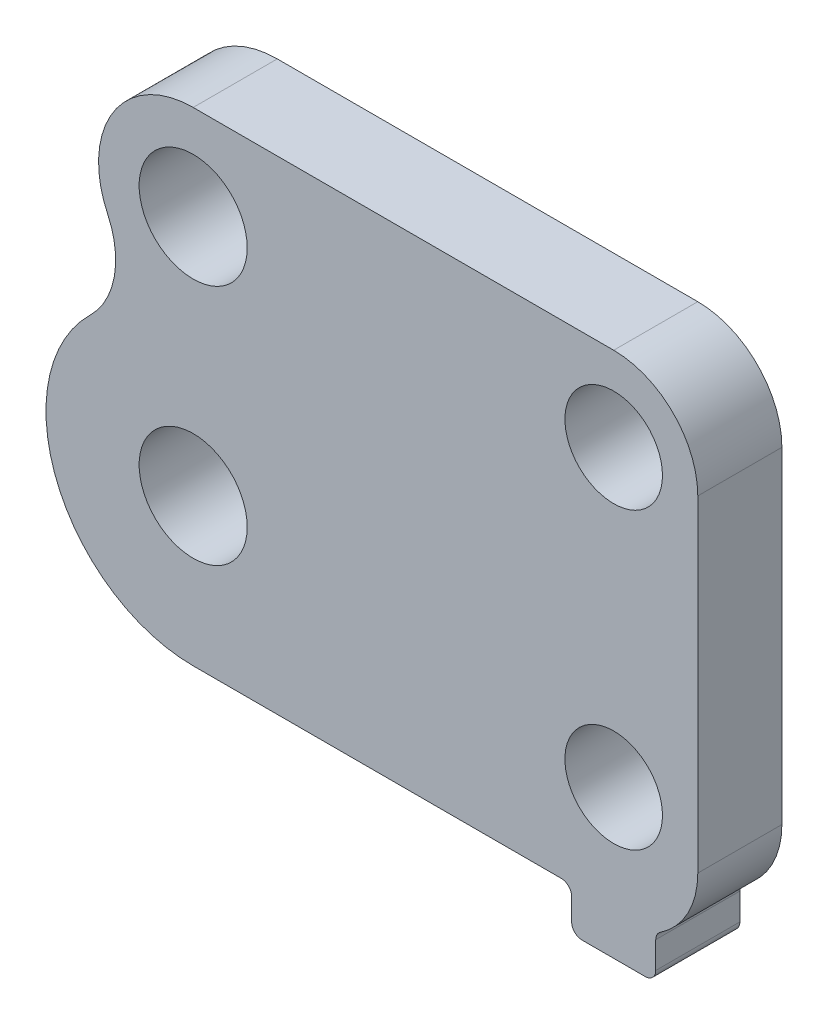
SolidWorks part; units mm, degrees
material "ABS"
ref_plane "Front Plane" through (0, 0, 0) normal (0, 0, 1) x (1, 0, 0)
ref_plane "Top Plane" through (0, 0, 0) normal (0, 1, 0) x (1, 0, 0)
ref_plane "Right Plane" through (0, 0, 0) normal (1, 0, 0) x (0, 0, -1)
sketch "Sketch2" plane through (0, 0, 0) normal (0, 0, 1) x (1, 0, 0)
  line L0 (0, 5.5562) -> (12.7, 5.5562)
  line L1 (12.7, 5.5562) -> (12.7, -5.5562) construction
  line L2 (12.7, -5.5562) -> (0, -5.5562)
  line L3 (12.7, 5.5562) -> (12.7, 13.4938)
  line L4 (12.7, 13.4938) -> (19.05, 13.4937)
  line L5 (19.05, 13.4937) -> (19.05, -5.5562)
  line L6 (19.05, -5.5562) -> (12.7, -5.5562)
  line L7 (15.875, 9.525) -> (15.875, -1.5875) construction
  line L8 (14.2875, -5.5562) -> (14.2875, -7.1818)
  line L9 (14.2875, -7.1818) -> (17.4625, -7.1818)
  line L10 (17.4625, -7.1818) -> (17.4625, -5.5562)
  line L11 (0, 0) -> (0, -9.1281) construction
  line L12 (7.1437, 12.7) -> (19.05, 12.7)
  line L13 (0, 12.7) -> (7.1437, 12.7)
  circle A0 centre (0, 0) radius 1.7859
  circle A1 centre (0, 0) radius 5.5562
  circle A2 centre (0, 9.1281) radius 1.7859
  circle A3 centre (0, 9.1281) radius 3.5719
  circle A4 centre (0, 0) radius 9.1281 construction
  circle A5 centre (15.875, 9.525) radius 1.5875
  circle A6 centre (15.875, -1.5875) radius 1.5875
  circle A7 centre (-6.1005, 6.2465) radius 3.175
  circle A8 centre (7.1437, 9.1281) radius 3.5719
  circle A9 centre (0, 0) radius 12.7 construction
  circle A10 centre (7.1437, 9.1281) radius 1.7859 construction
  point P17 (15.875, 3.9688)
  point P18 (19.05, 3.9688)
  point P21 (15.875, -5.5562)
  point P25 (15.875, -7.1818)
  dimension "D1" = 3.5719
  dimension "D2" = 11.1125
  dimension "D5" = 7.1437
  dimension "D7" = 3.175
  dimension "D6" = 6.35
  dimension "D3" = 11.1125
  dimension "D4" = 6.35
  dimension "D8" = 3.175
  dimension "D9" = 1.6256
  dimension "D10" = 19.05
sketch "Sketch3" plane through (0, 0, 0) normal (0, 0, 1) x (1, 0, 0)
  line L0 (7.1437, 12.7) -> (19.05, 12.7)
  line L1 (12.7, 13.4938) -> (19.05, 13.4937)
  line L2 (0, -5.5562) -> (19.05, -5.5562)
  line L3 (19.05, -5.5562) -> (19.05, 13.4937)
  line L4 (12.7, 5.5562) -> (12.7, 13.4938) construction
  line L5 (12.7, 12.7) -> (12.7, 13.4938)
  line L6 (7.1437, 12.7) -> (19.05, 12.7) construction
  line L7 (14.2875, -5.5562) -> (14.2875, -7.1818)
  line L8 (14.2875, -7.1818) -> (17.4625, -7.1818)
  line L9 (17.4625, -7.1818) -> (17.4625, -5.5562)
  line L10 (0, 12.7) -> (7.1437, 12.7)
  circle A0 centre (0, 0) radius 5.5562
  circle A1 centre (0, 0) radius 5.5562 construction
  circle A3 centre (-6.1005, 6.2465) radius 3.175
  circle A6 centre (15.875, 9.525) radius 1.8415
  circle A7 centre (15.875, -1.5875) radius 1.8415
  circle A8 centre (15.875, 9.525) radius 1.5875 construction
  circle A9 centre (15.875, -1.5875) radius 1.5875 construction
  circle A13 centre (-6.1005, 6.2465) radius 3.175 construction
  circle A15 centre (7.1437, 9.1281) radius 3.5719
  circle A16 centre (0, 9.1281) radius 3.5719
  circle A17 centre (0, 9.1281) radius 3.5719 construction
  circle A18 centre (0, 9.1281) radius 2.0399
  circle A21 centre (0, 0) radius 2.0399
  circle A22 centre (0, 0) radius 1.7859 construction
  circle A23 centre (0, 9.1281) radius 1.7859 construction
  dimension "D1" = 0.254
  dimension "D2" = 0.254
  dimension "D3" = 0.254
  dimension "D4" = 0.254
extrude "Boss-Extrude1" add sketch "Sketch3" along normal blind 3.175 contours A16 A0 L2 L3 L0 A15 A7 A6 | A15 | A0 A21 | L8 L9 L2 L7 | A16 | A16 A3 A0 | A16 A15 L10 region at (3.5719, 11.9022, 0) region at (11.883, 2.56, 0) region at (7.1437, 9.1281, 0) region at (2.4543, 11.5824, 0) region at (-2.3434, 5.6656, 0) region at (3.8177, 3.8177, 0) region at (15.875, -6.369, 0)
fillet "Fillet1" radius 3.175 2 edges at (19.05, -5.5562, 1.5875) (19.05, 12.7, 1.5875)
fillet "Fillet2" radius 0.3969 4 edges at (17.4625, -5.5562, 1.5875) (17.4625, -7.1818, 1.5875) (14.2875, -7.1818, 1.5875) (14.2875, -5.5562, 1.5875)
